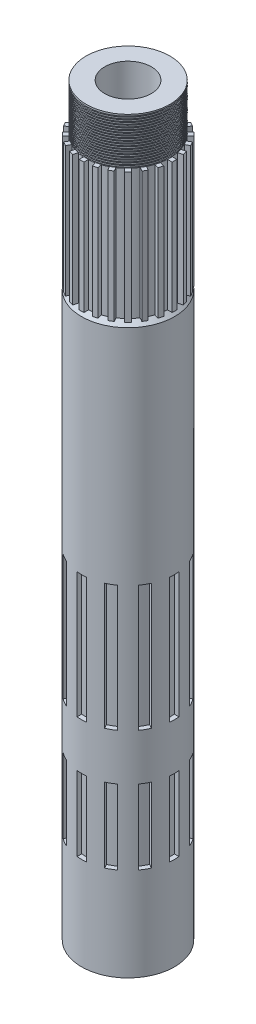
SolidWorks part; units mm, degrees
material "AISI 8620 Steel, carburized"
ref_plane "Front Plane" through (0, 0, 0) normal (1, 0, 0) x (0, 1, 0)
ref_plane "Top Plane" through (0, 0, 0) normal (0, 0, 1) x (0, 1, 0)
ref_plane "Right Plane" through (0, 0, 0) normal (0, 1, 0) x (-1, 0, 0)
sketch "Sketch1" plane through (0, 0, 0) normal (1, 0, 0) x (0, 1, 0)
  line L0 (-77.4599, 0) -> (178.3415, 0) construction
  line L1 (0, 0) -> (0, 10)
  line L2 (0, 10) -> (121, 10)
  line L3 (160, 9) -> (160, 0)
  line L4 (121, 20.3816) -> (121, -5.6566) construction
  line L5 (122, 20.3816) -> (122, -7.8342) construction
  line L6 (94, 20.3816) -> (94, -6.9683) construction
  line L7 (0, 4) -> (137.5, 4)
  line L8 (137.5, 5) -> (137.5, 0)
  line L9 (137.5, 5) -> (160, 5)
  line L10 (94, 10) -> (94, 9)
  line L11 (94, 9) -> (160, 9)
  line L12 (121, 10) -> (122, 9)
  line L13 (122, 9) -> (122, 10)
  line L14 (122, 10) -> (94, 10)
  line L16 (160, 10) -> (160, 9)
  point P13 (121, 10)
  dimension "D1" = 160
  dimension "D2" = 121
  dimension "D3" = 1
  dimension "D4" = 28
  dimension "D5" = 20
  dimension "D6" = 8
  dimension "D7" = 22.5
  dimension "D8" = 10
  dimension "D9" = 18
  dimension "D10" = 1
revolve "Revolve1" add sketch "Sketch1" angle 360 about L0 region at (0, 74.6657, 6.8752) region at (0, 107.7515, 9.497)
sketch "Sketch2" plane through (0, 0, 0) normal (1, 0, 0) x (0, 1, 0)
  line L0 (-5.4748, 0) -> (-81.9263, 0) construction
  line L1 (20, 1) -> (36, 1)
  line L2 (20, 1) -> (20, -1)
  line L3 (20, -1) -> (36, -1)
  line L4 (36, 1) -> (36, -1)
  line L5 (0, 10) -> (0, -10) construction
  line L7 (46, 1) -> (73, 1)
  line L8 (46, 1) -> (46, -1)
  line L9 (46, -1) -> (73, -1)
  line L10 (73, 1) -> (73, -1)
  point P9 (20, 0)
  dimension "D1" = 2
  dimension "D2" = 1
  dimension "D3" = 16
  dimension "D4" = 20
  dimension "D5" = 2
  dimension "D6" = 10
  dimension "D7" = 27
  dimension "D8" = 1
extrude "Cut-Extrude1" cut sketch "Sketch2" against normal blind 1 from surface starting at face at (0, 121, -10)
pattern_circular "CirPattern1" count 12 over 360 about axis through (0, 0, 0) along (0, -1, 0) of "Cut-Extrude1"
sketch "Sketch6" [suppressed] plane through (0, 94, 0) normal (0, 1, 0) x (-1, 0, 0)
  circle A1 centre (0, 0) radius 10
  circle A2 centre (0, 0) radius 9
  dimension "D2" = 20
  dimension "D1" = 1
ref_plane "Plane1" through (7, 0, 0) normal (1, 0, 0) x (0, 1, 0)
extrude "Boss-Extrude4" [suppressed] add sketch "Sketch6" along normal blind 28
sketch "Sketch5" plane through (7, 0, 0) normal (1, 0, 0) x (0, 1, 0)
  line L0 (0, 0) -> (103.9299, 0) construction
  line L1 (122, 0.5) -> (122, -0.5)
  line L2 (122, 0.5) -> (150, 0.5)
  line L4 (122, -0.5) -> (150, -0.5)
  line L5 (150, 0.5) -> (150, -0.5)
  line L9 (122, -9) -> (122, 9) construction
  dimension "D1" = 0.5
  dimension "D2" = 1
  dimension "D3" = 28
extrude "Boss-Extrude3" add sketch "Sketch5" along normal blind 2.99
pattern_circular "CirPattern3" count 24 over 360 about axis through (0, 122, 0) along (0, -1, 0) of "Boss-Extrude3"
ref_axis "Axis1" through (0, 168, 0) along (0, -1, 0)
sketch "Sketch9" plane through (0, 160, 0) normal (0, 1, 0) x (-1, 0, 0)
  circle A0 centre (0, 0) radius 10
  circle A1 centre (0, 0) radius 10.0025
  dimension "D1" = 20
extrude "Cut-Extrude5" [suppressed] cut sketch "Sketch9" against normal blind 41 contours A1 A0
thread "Thread1" pitch 0.25 method cut profile "Thread Profile1" start angle 0, offset 0, length 0, pitch 0.5, diameter 18
ref_plane "Plane2" through (-9, 160, 0) normal (0, 0, 1) x (-1, 0, 0)
sketch "Thread Profile1" plane through (-9, 160, 0) normal (0, 0, 1) x (-1, 0, 0)
  line L0 (0, 0) -> (0, 0.25) construction
  line L11 (0, 0) -> (0, 0.2187)
  line L12 (0, 0.2187) -> (-0.1353, 0.1406)
  line L13 (-0.1353, 0.1406) -> (-0.1353, 0.0781)
  line L15 (-0.1353, 0.0781) -> (0, 0)
  line L17 (-0.1353, 0.1094) -> (0, 0.1094) construction
  point P2 (0, 0)
  dimension "Pitch" = 0.25
  dimension "Profile_Angle" = 60
  dimension "Profile_Land" = 0.0625
  dimension "Profile_Height" = 0.1353
